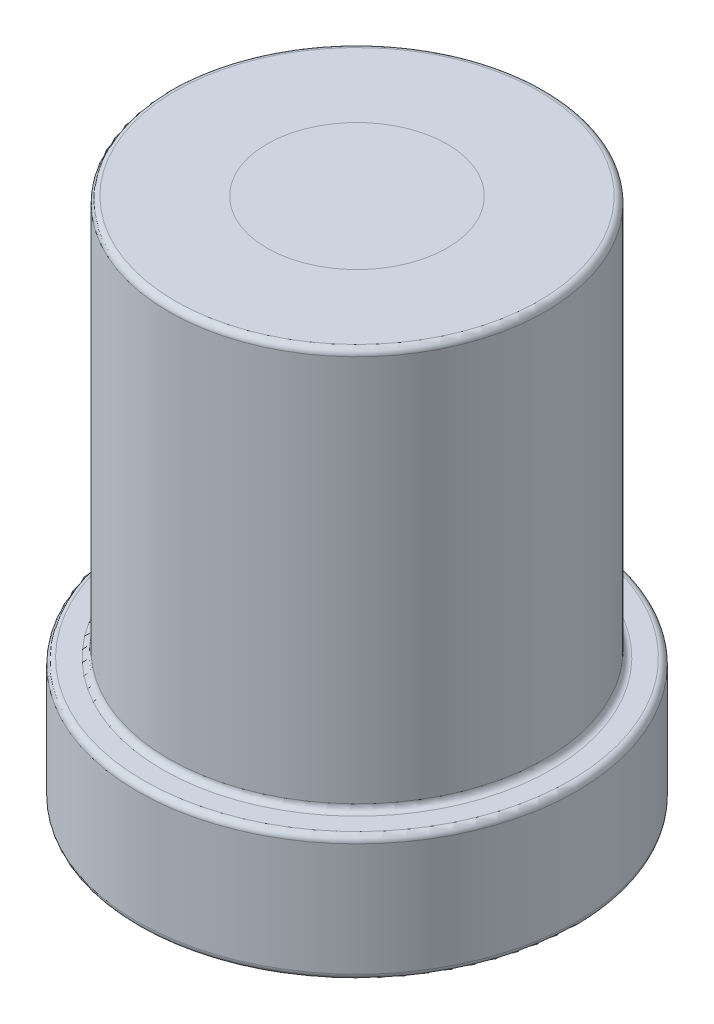
SolidWorks part; units mm, degrees
ref_plane "Front Plane" through (0, 0, 0) normal (0, 0, 1) x (1, 0, 0)
ref_plane "Top Plane" through (0, 0, 0) normal (0, 1, 0) x (1, 0, 0)
ref_plane "Right Plane" through (0, 0, 0) normal (1, 0, 0) x (0, 0, -1)
sketch "Sketch1" plane through (0, 0, 0) normal (0, 1, 0) x (1, 0, 0)
  circle A0 centre (0, 0) radius 7
  dimension "D1" = 14
extrude "Boss-Extrude1" add sketch "Sketch1" along normal blind 4
sketch "Sketch2" plane through (0, 4, 0) normal (0, 1, 0) x (1, 0, 0)
  circle A0 centre (0, 0) radius 6
  dimension "D1" = 12
extrude "Boss-Extrude2" add sketch "Sketch2" along normal blind 12.75
sketch "Sketch3" plane through (0, 16.75, 0) normal (0, 1, 0) x (1, 0, 0)
  circle A0 centre (0, 0) radius 2.875
  dimension "D1" = 5.75
extrude "Cut-Extrude1" cut sketch "Sketch3" against normal through all
sketch "Sketch4" plane through (0, 0, 0) normal (0, -1, 0) x (-1, 0, 0)
  circle A0 centre (0, 0) radius 4.4
  dimension "D1" = 8.8
extrude "Cut-Extrude2" cut sketch "Sketch4" against normal blind 3
chamfer "Chamfer1" distance 1.3 distance2 0.5 1 edges at (0, 0, -4.4) first distance on face at (0, 0, -4.4)
sketch "Sketch5" plane through (0, 3, 0) normal (0, -1, 0) x (-1, 0, 0)
  circle A0 centre (0, 0) radius 4.4
extrude "Boss-Extrude3" add sketch "Sketch5" along normal blind 2 separate body
dome "Dome1" faces to dome 1 distance 0.5 reverse direction no elliptical dome no face at (0, 1, -4.4) parameters "D1"=0.5
fillet "Fillet1" radius 0.2 6 edges at (0, 0, 5.7) (0, 0.5, 4.4) (0, 16.75, 6) (0, 4, 6) (0, 4, 7) (0, 0, 7)
sketch "Sketch6" plane through (0, 16.75, 0) normal (0, 1, 0) x (1, 0, 0)
  circle A0 centre (0, 0) radius 2.875
extrude "Boss-Extrude4" add sketch "Sketch6" against normal blind 2 separate body
